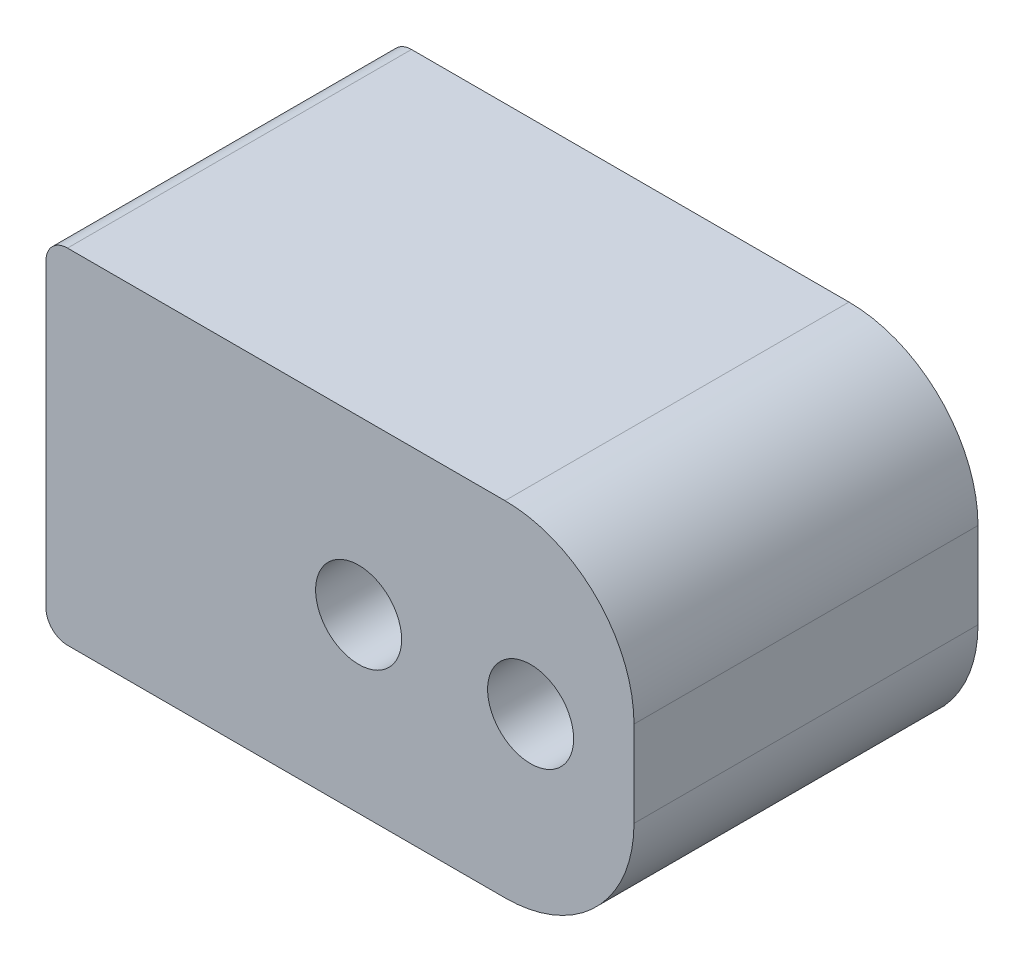
SolidWorks part; units mm, degrees
ref_plane "Front" through (0, 0, 0) normal (0, 0, 1) x (1, 0, 0)
ref_plane "Top" through (0, 0, 0) normal (0, 1, 0) x (1, 0, 0)
ref_plane "Right" through (0, 0, 0) normal (1, 0, 0) x (0, 0, -1)
sketch "Sketch1" plane through (0, 0, 0) normal (0, 0, 1) x (1, 0, 0)
  line L0 (-7.27, 4) -> (0, 4)
  line L1 (0, -4) -> (-7.27, -4)
  line L2 (-7.27, 4) -> (-7.27, -4)
  line L3 (55, 0) -> (-55, 0) construction
  line L4 (0, 4) -> (6.4045, 4)
  line L5 (0, 4) -> (0, -4)
  line L6 (0, -4) -> (6.4045, -4)
  line L7 (6.4045, 4) -> (6.4045, -4)
  circle A0 centre (0, 0) radius 4
  circle A1 centre (0, 0) radius 1
  circle A2 centre (4, 0) radius 1
  dimension "D1" = 8
  dimension "D3" = 2
  dimension "D4" = 4
  dimension "D2" = 7.27
extrude "Boss-Extrude1" add sketch "Sketch1" along normal blind 8 contours A0 L0 L2 L1 | A1 L5 A0 | A1 L5 A0 | A0 A2 L6 L7 L4 region at (-5.1093, 0, 0) region at (1.6632, 0, 0) region at (-1.7825, 0, 0) region at (3.2023, 3.8975, 0)
sketch "Sketch2" plane through (-7.27, 0, 0) normal (-1, 0, 0) x (0, 0, 1)
  line L5 (4.4, 0) -> (-4.4, 0) construction
  line L6 (8, 4) -> (0, 4) construction
  line L7 (8, 4) -> (0, 4)
  circle A0 centre (4, 0) radius 3.15
  point P8 (4, 4)
  dimension "D1" = 6.3
extrude "Cut-Extrude1" cut sketch "Sketch2" against normal blind 3.3 from offset 0.4 contours A0 region at (-7.27, 0, 4) offset against normal yes
fillet "Fillet2" radius 0.5 2 edges at (-7.27, -4, 4) (-7.27, 4, 4)
fillet "Fillet3" radius 3 2 edges at (6.4045, -4, 4) (6.4045, 4, 4)
